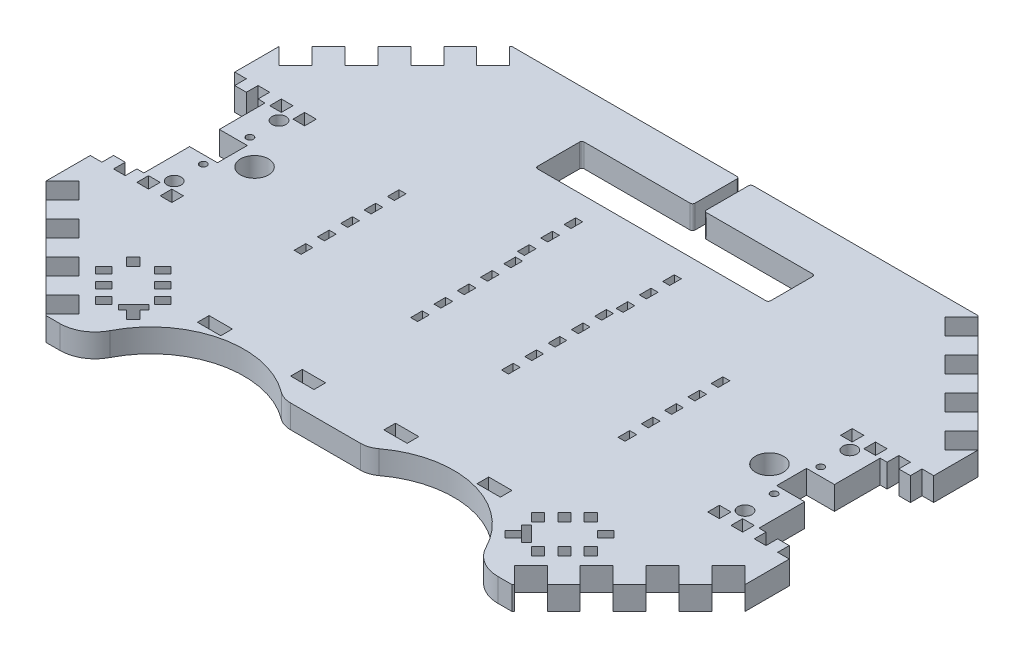
SolidWorks part; units mm, degrees
material "Balsa"
ref_plane "Plan de face" through (0, 0, 0) normal (0, 0, 1) x (1, 0, 0)
ref_plane "Plan de dessus" through (0, 0, 0) normal (0, 1, 0) x (1, 0, 0)
ref_plane "Plan de droite" through (0, 0, 0) normal (1, 0, 0) x (0, 0, -1)
sketch "Esquisse1" plane through (0, 0, 0) normal (0, 1, 0) x (1, 0, 0)
  line L1 (-150, 100) -> (150, 100)
  line L2 (-150, 100) -> (-150, -100)
  line L3 (-150, -100) -> (150, -100)
  line L4 (150, 100) -> (150, -100)
  dimension "D1" = 300
  dimension "D2" = 200
  dimension "D3" = 150
  dimension "D4" = 100
extrude "Boss.-Extru.1" add sketch "Esquisse1" along normal blind 10
sketch "Esquisse2" plane through (0, 10, 0) normal (0, 1, 0) x (1, 0, 0)
  line L0 (-100, 100) -> (-150, 50)
  line L1 (150, 100) -> (-150, 100) construction
  line L2 (-150, 100) -> (-150, -100) construction
  line L3 (-150, 50) -> (-150, 100)
  line L4 (-150, 100) -> (-100, 100)
  line L5 (150, 100) -> (150, 50)
  line L6 (150, -100) -> (150, 100) construction
  line L7 (150, 50) -> (100, 100)
  line L8 (100, 100) -> (150, 100)
  line L9 (150, -100) -> (150, -50)
  line L10 (150, -50) -> (100, -100)
  line L11 (-150, -100) -> (150, -100) construction
  line L12 (100, -100) -> (150, -100)
  line L13 (-100, -100) -> (-150, -100)
  line L14 (-150, -100) -> (-150, -50)
  line L15 (-150, -50) -> (-100, -100)
  dimension "D1" = 50
  dimension "D2" = 50
  dimension "D3" = 50
  dimension "D4" = 50
  dimension "D5" = 50
  dimension "D6" = 50
  dimension "D7" = 50
  dimension "D8" = 50
extrude "Enlèv. mat.-Extru.1" cut sketch "Esquisse2" against normal blind 10
sketch "Esquisse3" plane through (0, 10, 0) normal (0, 1, 0) x (1, 0, 0)
  line L0 (-100, -100) -> (100, -100) construction
  circle A1 centre (-45, -110) radius 40
  circle A2 centre (45, -110) radius 40
  dimension "80" = 80
  dimension "D3" = 80
  dimension "D4" = 10
  dimension "D5" = 10
  dimension "D6" = 90
  dimension "D7" = 45
sketch "Esquisse4" plane through (0, 10, 0) normal (0, 1, 0) x (1, 0, 0)
  line L1 (-21, 22.5) -> (-18, 22.5)
  line L2 (-21, 22.5) -> (-21, 17.5)
  line L3 (-21, 17.5) -> (-18, 17.5)
  line L4 (-18, 22.5) -> (-18, 17.5)
  dimension "D1" = 5
  dimension "D2" = 3
  dimension "D3" = 18
  dimension "D4" = 17.5
extrude "Enlèv. mat.-Extru.3" cut sketch "Esquisse4" against normal blind 10 contours L1 L4 L3 L2
pattern_linear "Répétition linéaire1" count 5 spacing 10 along (0, 0, 1) count 2 spacing 50 along (-1, 0, 0) of "Enlèv. mat.-Extru.3"
sketch "Esquisse8" plane through (0, 10, 0) normal (0, 1, 0) x (1, 0, 0)
  line L0 (-150, 50) -> (-150, -50) construction
  circle A0 centre (-122.5, 22.5) radius 3
  circle A1 centre (-122.5, -22.5) radius 3
  dimension "D1" = 6
  dimension "D2" = 6
  dimension "D4" = 22.5
  dimension "D6" = 27.5
  dimension "D5" = 27.5
  dimension "D3" = 45
extrude "Enlèv. mat.-Extru.6" cut sketch "Esquisse8" against normal blind 10
sketch "Esquisse14" plane through (0, 10, 0) normal (0, 1, 0) x (1, 0, 0)
  circle A0 centre (-110.5, 0) radius 6
  circle A1 centre (-122.5, 22.5) radius 3 construction
  circle A2 centre (-122.5, 10) radius 1.5
  circle A3 centre (-122.5, -10) radius 1.5
  dimension "D1" = 12
  dimension "D3" = 3
  dimension "D4" = 3
  dimension "D5" = 20
  dimension "D6" = 10
  dimension "D7" = 0
  dimension "D2" = 12
extrude "Enlèv. mat.-Extru.13" cut sketch "Esquisse14" against normal blind 10
mirror "Symétrie1" about plane through (0, 0, 0) normal (1, 0, 0) of "Enlèv. mat.-Extru.13", "Enlèv. mat.-Extru.3", "Répétition linéaire1", "Enlèv. mat.-Extru.6"
extrude "Enlèv. mat.-Extru.7" cut sketch "Esquisse3" against normal blind 10 contours A1 | A2
fillet "Congé1" radius 15 4 edges at (83.7298, 5, 100) (6.2702, 5, 100) (-6.2702, 5, 100) (-83.7298, 5, 100)
sketch "Esquisse12" plane through (0, 10, 0) normal (0, 1, 0) x (1, 0, 0)
  line L0 (-150, 50) -> (-142.9289, 57.0711)
  line L1 (-150, 50) -> (-142.9289, 42.9289)
  line L2 (-142.9289, 57.0711) -> (-135.8579, 50)
  line L3 (-142.9289, 42.9289) -> (-135.8579, 50)
  line L4 (-150, 50) -> (-100, 100) construction
  dimension "D1" = 10
  dimension "D2" = 10
  dimension "D3" = 0
extrude "Enlèv. mat.-Extru.11" cut sketch "Esquisse12" against normal blind 10
pattern_linear "Répétition linéaire2" count 4 spacing 20 along (0.7071, 0, -0.7071) of "Enlèv. mat.-Extru.11"
mirror "Symétrie2" about plane through (0, 0, 0) normal (0, 0, 1) of "Répétition linéaire2", "Enlèv. mat.-Extru.11"
mirror "Symétrie3" about plane through (0, 0, 0) normal (1, 0, 0) of "Symétrie2", "Enlèv. mat.-Extru.11", "Répétition linéaire2"
sketch "Esquisse17" plane through (0, 10, 0) normal (0, 1, 0) x (1, 0, 0)
  line L0 (-3.9898, -100) -> (3.9898, -100) construction
  line L1 (-65, -65) -> (-55, -65)
  line L2 (-65, -65) -> (-65, -70)
  line L3 (-65, -70) -> (-55, -70)
  line L4 (-55, -65) -> (-55, -70)
  dimension "D1" = 10
  dimension "D2" = 5
  dimension "D3" = 35
  dimension "D4" = 65
extrude "Enlèv. mat.-Extru.16" cut sketch "Esquisse17" against normal blind 10
pattern_linear "Répétition linéaire3" count 4 spacing 40 along (1, 0, 0) of "Enlèv. mat.-Extru.16"
sketch "Esquisse21" plane through (0, 10, 0) normal (0, 1, 0) x (1, 0, 0)
  line L0 (-25, -70) -> (-15, -70) construction
  line L1 (-18.5425, -80) -> (25, -80)
  line L2 (-18.5425, -80) -> (-18.5425, -100)
  line L3 (-18.5425, -100) -> (25, -100)
  line L4 (25, -80) -> (25, -100)
  arc A0 (-9.3711, -91.8182) -> (-80.6289, -91.8182) centre (-45, -110) ccw construction
  arc A1 (80.6289, -91.8182) -> (9.3711, -91.8182) centre (45, -110) ccw construction
  dimension "D1" = 10
  dimension "D2" = 20
  dimension "D3" = 20
extrude "Enlèv. mat.-Extru.20" cut sketch "Esquisse21" against normal blind 10
fillet "Congé2" radius 10 2 edges at (18.5425, 5, 80) (-18.5425, 5, 80)
sketch "Esquisse22" plane through (0, 10, 0) normal (0, 1, 0) x (1, 0, 0)
  line L0 (-135, 31) -> (-135, 26)
  line L1 (-150, 50) -> (-150, -50) construction
  line L3 (-115, 26) -> (-120, 26)
  line L4 (-125, 26) -> (-130, 26)
  line L5 (-140, 31) -> (-135, 31)
  line L6 (-135, 26) -> (-140, 26)
  line L7 (-140, 31) -> (-140, 26)
  line L8 (-150, 31) -> (-145, 31)
  line L9 (-150, 31) -> (-150, 26)
  line L10 (-150, 26) -> (-145, 26)
  line L11 (-145, 31) -> (-145, 26)
  line L12 (-125, 31) -> (-125, 26)
  line L13 (-130, 31) -> (-125, 31)
  line L14 (-130, 31) -> (-130, 26)
  line L15 (-115, 31) -> (-115, 26)
  line L16 (-120, 31) -> (-115, 31)
  line L17 (-120, 31) -> (-120, 26)
  line L21 (-115, 0) -> (-150, 0) construction
  line L22 (0, 17.7082) -> (0, -16.4392) construction
  line L26 (-120, -31) -> (-120, -26)
  line L27 (-120, -31) -> (-115, -31)
  line L28 (-115, -31) -> (-115, -26)
  line L29 (-130, -31) -> (-130, -26)
  line L30 (-130, -31) -> (-125, -31)
  line L31 (-125, -31) -> (-125, -26)
  line L32 (-145, -31) -> (-145, -26)
  line L33 (-150, -26) -> (-145, -26)
  line L34 (-150, -31) -> (-150, -26)
  line L35 (-150, -31) -> (-145, -31)
  line L36 (-140, -31) -> (-140, -26)
  line L37 (-135, -26) -> (-140, -26)
  line L38 (-140, -31) -> (-135, -31)
  line L39 (-125, -26) -> (-130, -26)
  line L40 (-115, -26) -> (-120, -26)
  line L42 (-135, -31) -> (-135, -26)
  line L43 (135, -31) -> (135, -26)
  line L45 (115, -26) -> (120, -26)
  line L46 (125, -26) -> (130, -26)
  line L47 (140, -31) -> (135, -31)
  line L48 (135, -26) -> (140, -26)
  line L49 (140, -31) -> (140, -26)
  line L50 (150, -31) -> (145, -31)
  line L51 (150, -31) -> (150, -26)
  line L52 (150, -26) -> (145, -26)
  line L53 (145, -31) -> (145, -26)
  line L54 (125, -31) -> (125, -26)
  line L55 (130, -31) -> (125, -31)
  line L56 (130, -31) -> (130, -26)
  line L57 (115, -31) -> (115, -26)
  line L58 (120, -31) -> (115, -31)
  line L59 (120, -31) -> (120, -26)
  line L66 (120, 31) -> (120, 26)
  line L67 (120, 31) -> (115, 31)
  line L68 (115, 31) -> (115, 26)
  line L69 (130, 31) -> (130, 26)
  line L70 (130, 31) -> (125, 31)
  line L71 (125, 31) -> (125, 26)
  line L72 (145, 31) -> (145, 26)
  line L73 (150, 26) -> (145, 26)
  line L74 (150, 31) -> (150, 26)
  line L75 (150, 31) -> (145, 31)
  line L76 (140, 31) -> (140, 26)
  line L77 (135, 26) -> (140, 26)
  line L78 (140, 31) -> (135, 31)
  line L79 (125, 26) -> (130, 26)
  line L80 (115, 26) -> (120, 26)
  line L82 (135, 31) -> (135, 26)
  line L83 (-105, 31) -> (-105, 26) [skipped]
  line L84 (-110, 31) -> (-105, 31) [skipped]
  line L85 (-110, 31) -> (-110, 26) [skipped]
  dimension "D1" = 35
  dimension "D4" = 5
  dimension "D5" = 5
  dimension "D6" = 5
extrude "Enlèv. mat.-Extru.21" cut sketch "Esquisse22" against normal blind 10
sketch "Esquisse23" plane through (0, 10, 0) normal (0, 1, 0) x (1, 0, 0)
  line L0 (100, 100) -> (-100, 100) construction
  line L1 (-50, 80) -> (50, 80)
  line L2 (-50, 80) -> (-50, 60)
  line L3 (-50, 60) -> (50, 60)
  line L4 (50, 80) -> (50, 60)
  dimension "D1" = 20
  dimension "D2" = 100
  dimension "D3" = 50
  dimension "D4" = 20
extrude "Enlèv. mat.-Extru.22" cut sketch "Esquisse23" against normal blind 10
sketch "Esquisse24" plane through (0, 10, 0) normal (0, 1, 0) x (1, 0, 0)
  line L0 (50, 80) -> (-50, 80) construction
  line L1 (2.5, 80) -> (-2.5, 80)
  line L2 (2.5, 80) -> (2.5, 100)
  line L3 (2.5, 100) -> (-2.5, 100)
  line L4 (-2.5, 80) -> (-2.5, 100)
  line L5 (100, 100) -> (-100, 100) construction
  dimension "D1" = 97.5
  dimension "D2" = 97.5
  dimension "D3" = 5
extrude "Enlèv. mat.-Extru.23" cut sketch "Esquisse24" against normal blind 10
fillet "Congé3" radius 1 8 edges at (-50, 5, -80) (-50, 5, -60) (50, 5, -60) (50, 5, -80) (2.5, 5, -80) (-2.5, 5, -100) (2.5, 5, -100) (-2.5, 5, -80)
sketch "Esquisse26" plane through (0, 10, 0) normal (0, 1, 0) x (1, 0, 0)
  line L0 (0, 0) -> (0, 60) construction
  line L1 (-49, 60) -> (49, 60) construction
  line L2 (22.67, 40) -> (22.67, 35)
  line L3 (22.67, 50) -> (19.67, 50)
  line L4 (22.67, 50) -> (22.67, 45)
  line L5 (22.67, 45) -> (19.67, 45)
  line L6 (19.67, 50) -> (19.67, 45)
  line L7 (22.67, 35) -> (19.67, 35)
  line L8 (19.67, 40) -> (19.67, 35)
  line L9 (22.67, 40) -> (19.67, 40)
  line L10 (22.67, 30) -> (22.67, 25)
  line L11 (22.67, 25) -> (19.67, 25)
  line L12 (19.67, 30) -> (19.67, 25)
  line L13 (22.67, 30) -> (19.67, 30)
  line L14 (-22.67, 30) -> (-19.67, 30)
  line L15 (-19.67, 30) -> (-19.67, 25)
  line L16 (-22.67, 25) -> (-19.67, 25)
  line L17 (-22.67, 30) -> (-22.67, 25)
  line L18 (-22.67, 40) -> (-19.67, 40)
  line L19 (-19.67, 40) -> (-19.67, 35)
  line L20 (-22.67, 35) -> (-19.67, 35)
  line L21 (-19.67, 50) -> (-19.67, 45)
  line L22 (-22.67, 45) -> (-19.67, 45)
  line L23 (-22.67, 50) -> (-22.67, 45)
  line L24 (-22.67, 50) -> (-19.67, 50)
  line L25 (-22.67, 40) -> (-22.67, 35)
  dimension "D1" = 19.67
  dimension "D2" = 5
  dimension "D3" = 3
  dimension "D4" = 10
  dimension "D5" = 3
extrude "Enlèv. mat.-Extru.25" cut sketch "Esquisse26" against normal blind 10
sketch "Esquisse28" plane through (0, 0, 0) normal (0, -1, 0) x (1, 0, 0)
  line L0 (87.2025, 84.5132) -> (108.0622, 63.6535)
  line L1 (108.0622, 63.6535) -> (98.8698, 54.4612)
  line L2 (98.8698, 54.4612) -> (78.0102, 75.3208)
  line L3 (78.0102, 75.3208) -> (87.2025, 84.5132)
  line L4 (87.2025, 84.5132) -> (86.8428, 84.8356)
  line L5 (0, 0) -> (0, 18.0192) construction
  line L7 (-78.0102, 75.3208) -> (-87.2025, 84.5132)
  line L8 (-98.8698, 54.4612) -> (-78.0102, 75.3208)
  line L9 (-108.0622, 63.6535) -> (-98.8698, 54.4612)
  line L10 (-87.2025, 84.5132) -> (-108.0622, 63.6535)
  dimension "D1" = 29.5
  dimension "D2" = 13
  dimension "D3" = 10
sketch "Esquisse29" plane through (0, 0, 0) normal (0, -1, 0) x (1, 0, 0)
  line L0 (-98.8974, 75.3484) -> (-87.2095, 63.6605) construction
  line L1 (-103.466, 59.0573) -> (-82.6063, 79.917) construction
  line L2 (-100.9911, 64.3606) -> (-104.5267, 60.8251)
  line L3 (-104.5267, 60.8251) -> (-101.6982, 57.9967)
  line L4 (86.4954, 82.3919) -> (88.6168, 80.2705)
  line L5 (-101.6982, 57.9967) -> (-98.1627, 61.5322)
  line L6 (-98.1627, 61.5322) -> (-100.9911, 64.3606)
  line L7 (-101.3447, 70.3711) -> (-104.8802, 73.9066)
  line L8 (-104.8802, 73.9066) -> (-107.7086, 71.0782)
  line L9 (-107.7086, 71.0782) -> (-104.1731, 67.5426)
  line L10 (-104.1731, 67.5426) -> (-101.3447, 70.3711)
  line L11 (-93.5665, 85.2203) -> (-96.3949, 82.3919)
  line L12 (-90.031, 81.6848) -> (-93.5665, 85.2203)
  line L13 (-92.8594, 78.8563) -> (-90.031, 81.6848)
  line L14 (-96.3949, 82.3919) -> (-92.8594, 78.8563)
  line L15 (-81.1921, 84.1596) -> (-78.3637, 81.3312)
  line L16 (-78.3637, 81.3312) -> (-81.8992, 77.7957)
  line L17 (-81.8992, 77.7957) -> (-84.7277, 80.6241)
  line L18 (-84.7277, 80.6241) -> (-81.1921, 84.1596)
  line L19 (-83.667, 69.6639) -> (-80.8386, 72.4924)
  line L20 (-80.8386, 72.4924) -> (-77.303, 68.9568)
  line L21 (-77.303, 68.9568) -> (-80.1315, 66.1284)
  line L22 (-80.1315, 66.1284) -> (-83.667, 69.6639)
  line L23 (-94.9807, 58.3502) -> (-92.1523, 61.1787)
  line L24 (-92.1523, 61.1787) -> (-88.6168, 57.6431)
  line L25 (-88.6168, 57.6431) -> (-91.4452, 54.8147)
  line L26 (-91.4452, 54.8147) -> (-94.9807, 58.3502)
  line L27 (-95.6878, 76.0279) -> (-99.2234, 79.5634)
  line L28 (-99.2234, 79.5634) -> (-102.0518, 76.735)
  line L29 (-102.0518, 76.735) -> (-98.5162, 73.1995)
  line L30 (-98.5162, 73.1995) -> (-95.6878, 76.0279)
  line L31 (-89.3239, 64.0071) -> (-86.4954, 66.8355)
  line L32 (-86.4954, 66.8355) -> (-82.9599, 63.3)
  line L33 (-82.9599, 63.3) -> (-85.7883, 60.4716)
  line L34 (-85.7883, 60.4716) -> (-89.3239, 64.0071)
  line L35 (88.6168, 80.2705) -> (82.0498, 73.7036)
  line L36 (82.0498, 73.7036) -> (79.9285, 75.825)
  line L37 (79.9285, 75.825) -> (81.8992, 77.7957)
  line L38 (81.8992, 77.7957) -> (81.8922, 77.7826)
  line L39 (-86.4954, 82.3919) -> (-88.6168, 80.2705)
  line L40 (-79.9285, 75.825) -> (-81.8992, 77.7957)
  line L41 (-82.0498, 73.7036) -> (-79.9285, 75.825)
  line L42 (-88.6168, 80.2705) -> (-82.0498, 73.7036)
  line L43 (0, 0) -> (0, 18.0192) construction
  line L44 (103.466, 59.0573) -> (82.6063, 79.917) construction
  line L45 (98.8974, 75.3484) -> (87.2095, 63.6605) construction
  line L46 (85.7883, 60.4716) -> (89.3239, 64.0071)
  line L47 (82.9599, 63.3) -> (85.7883, 60.4716)
  line L48 (86.4954, 66.8355) -> (82.9599, 63.3)
  line L49 (89.3239, 64.0071) -> (86.4954, 66.8355)
  line L50 (98.5162, 73.1995) -> (95.6878, 76.0279)
  line L51 (102.0518, 76.735) -> (98.5162, 73.1995)
  line L52 (99.2234, 79.5634) -> (102.0518, 76.735)
  line L53 (95.6878, 76.0279) -> (99.2234, 79.5634)
  line L54 (91.4452, 54.8147) -> (94.9807, 58.3502)
  line L55 (88.6168, 57.6431) -> (91.4452, 54.8147)
  line L56 (92.1523, 61.1787) -> (88.6168, 57.6431)
  line L57 (94.9807, 58.3502) -> (92.1523, 61.1787)
  line L58 (80.1315, 66.1284) -> (83.667, 69.6639)
  line L59 (77.303, 68.9568) -> (80.1315, 66.1284)
  line L60 (80.8386, 72.4924) -> (77.303, 68.9568)
  line L61 (83.667, 69.6639) -> (80.8386, 72.4924)
  line L62 (84.7277, 80.6241) -> (81.1921, 84.1596)
  line L63 (81.8992, 77.7957) -> (84.7277, 80.6241)
  line L64 (78.3637, 81.3312) -> (81.8992, 77.7957)
  line L65 (81.1921, 84.1596) -> (78.3637, 81.3312)
  line L66 (96.3949, 82.3919) -> (92.8594, 78.8563)
  line L67 (92.8594, 78.8563) -> (90.031, 81.6848)
  line L68 (90.031, 81.6848) -> (93.5665, 85.2203)
  line L69 (93.5665, 85.2203) -> (96.3949, 82.3919)
  line L70 (104.1731, 67.5426) -> (101.3447, 70.3711)
  line L71 (107.7086, 71.0782) -> (104.1731, 67.5426)
  line L72 (104.8802, 73.9066) -> (107.7086, 71.0782)
  line L73 (101.3447, 70.3711) -> (104.8802, 73.9066)
  line L74 (84.7277, 80.6241) -> (86.4954, 82.3919)
  line L75 (-84.7277, 80.6241) -> (-86.4954, 82.3919)
  line L82 (98.1627, 61.5322) -> (100.9911, 64.3606)
  line L83 (101.6982, 57.9967) -> (98.1627, 61.5322)
  line L84 (104.5267, 60.8251) -> (101.6982, 57.9967)
  line L85 (100.9911, 64.3606) -> (104.5267, 60.8251)
  dimension "D3" = 3
  dimension "D4" = 9.287
  dimension "D9" = 4
  dimension "D10" = 3
  dimension "D11" = 0
  dimension "D12" = 5
  dimension "D13" = 4
  dimension "D14" = 4
  dimension "D15" = 5
  dimension "D16" = 5
  dimension "D17" = 4
  dimension "D18" = 4
  dimension "D19" = 4
  dimension "D20" = 4
  dimension "D21" = 4
  dimension "D22" = 5
  dimension "D23" = 4
  dimension "D24" = 4
  dimension "D25" = 4
  dimension "D26" = 4
  dimension "D27" = 3
extrude "Enlèv. mat.-Extru.26" cut sketch "Esquisse29" against normal blind 10
sketch "Esquisse30" plane through (0, 0, 0) normal (0, -1, 0) x (1, 0, 0)
  line L0 (150, 26) -> (150, -26) construction
  line L1 (150, -26) -> (132, -26)
  line L2 (150, -26) -> (150, 26)
  line L3 (150, 26) -> (132, 26)
  line L4 (132, -26) -> (132, 26)
  line L5 (135, -26) -> (140, -26) construction
  line L6 (0, 0) -> (0, 18.0192) construction
  line L7 (-132, -26) -> (-132, 26)
  line L8 (-150, 26) -> (-132, 26)
  line L9 (-150, -26) -> (-150, 26)
  line L10 (-150, -26) -> (-132, -26)
  dimension "D1" = 52
  dimension "D2" = 0
  dimension "D3" = 18
extrude "Enlèv. mat.-Extru.27" cut sketch "Esquisse30" against normal blind 10
sketch "Esquisse32" plane through (0, 0, 0) normal (0, -1, 0) x (1, 0, 0)
  line L0 (132, 26) -> (132, -26) construction
  line L1 (132, -6.4) -> (120, -6.4)
  line L2 (132, -6.4) -> (132, 6.4)
  line L3 (132, 6.4) -> (120, 6.4)
  line L4 (120, -6.4) -> (120, 6.4)
  line L6 (125, -26) -> (130, -26) construction
  line L7 (0, 0) -> (0, 18.0192) construction
  line L8 (-120, -6.4) -> (-120, 6.4)
  line L9 (-132, 6.4) -> (-120, 6.4)
  line L10 (-132, -6.4) -> (-132, 6.4)
  line L11 (-132, -6.4) -> (-120, -6.4)
  dimension "D1" = 12.8
  dimension "D2" = 12
  dimension "D3" = 19.6
extrude "Enlèv. mat.-Extru.28" cut sketch "Esquisse32" against normal blind 10
